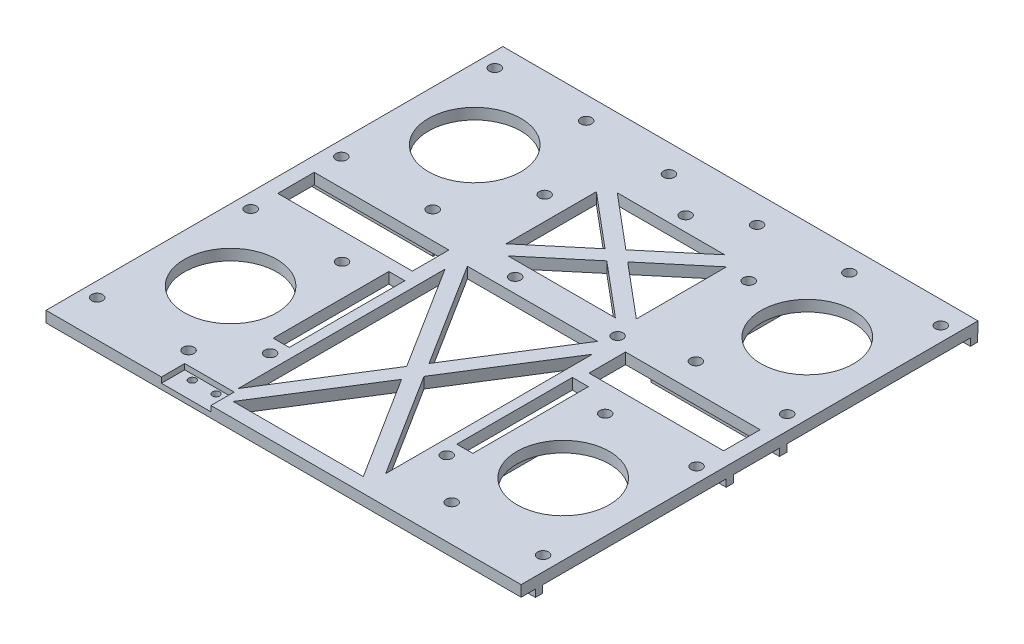
SolidWorks part; units mm, degrees
ref_plane "Front Plane" through (0, 0, 0) normal (0, 0, 1) x (1, 0, 0)
ref_plane "Top Plane" through (0, 0, 0) normal (0, 1, 0) x (1, 0, 0)
ref_plane "Right Plane" through (0, 0, 0) normal (1, 0, 0) x (0, 0, -1)
sketch "Sketch1" plane through (0, 0, 0) normal (0, 1, 0) x (1, 0, 0)
  line L1 (-65, 62.5) -> (65, 62.5)
  line L2 (-65, 62.5) -> (-65, -62.5)
  line L3 (-65, -62.5) -> (65, -62.5)
  line L4 (65, 62.5) -> (65, -62.5)
  line L5 (-65, 62.5) -> (65, -62.5) construction
  line L6 (-65, -62.5) -> (65, 62.5) construction
  point P0 (0, 0)
  dimension "D1" = 130
  dimension "D2" = 125
extrude "Boss-Extrude1" add sketch "Sketch1" along normal blind 5
sketch "Sketch2" plane through (0, 5, 0) normal (0, 1, 0) x (1, 0, 0)
  line L1 (-65, -62.5) -> (65, -62.5) construction
  line L2 (-65, 62.5) -> (-65, -62.5) construction
  circle A0 centre (-61, -52.5) radius 1.5
  circle A1 centre (-36, -52.5) radius 1.5
  circle A2 centre (-36, -10.5) radius 1.5
  circle A3 centre (-61, -10.5) radius 1.5
  circle A4 centre (-45.5, -31.5) radius 12.65
  dimension "D2" = 25.3
  dimension "D7" = 3
  dimension "D8" = 3
  dimension "D9" = 3
  dimension "D10" = 3
  dimension "D1" = 19.5
  dimension "D3" = 31
  dimension "D4" = 4
  dimension "D5" = 10
  dimension "D6" = 10
  dimension "D11" = 4
  dimension "D12" = 42
  dimension "D13" = 42
  dimension "D14" = 25
  dimension "D15" = 25
extrude "Cut-Extrude1" cut sketch "Sketch2" against normal blind 10
ref_plane "Plane1" through (0, 0, 0) normal (-1, 0, 0) x (0, 0, 1)
ref_plane "Plane2" through (0, 0, 0) normal (0, 0, 1) x (1, 0, 0)
mirror "Mirror3" about plane through (0, 0, 0) normal (-1, 0, 0) of "Cut-Extrude1"
sketch "Sketch4" plane through (0, 5, 0) normal (0, 1, 0) x (1, 0, 0)
  line L0 (0, 62.5) -> (0, 47.5) construction
  line L1 (65, 62.5) -> (-65, 62.5) construction
  line L2 (-12.0498, 55) -> (12.0498, 55) construction
  circle A0 centre (0, 47.5) radius 1.5
  circle A1 centre (12.0498, 55) radius 1.5
  circle A2 centre (-12.0498, 55) radius 1.5
  point P9 (0, 55)
  dimension "D2" = 3
  dimension "D3" = 3
  dimension "D4" = 3
  dimension "D1" = 15
  dimension "D5" = 24.0996
extrude "Cut-Extrude3" cut sketch "Sketch4" against normal blind 10
sketch "Sketch5" plane through (0, 0, 0) normal (0, -1, 0) x (1, 0, 0)
  line L0 (-58.15, 31.5) -> (-65, 31.5) construction
  line L1 (-65, -62.5) -> (-65, 62.5) construction
  line L2 (-65, 56.6) -> (-65, 6.4)
  line L3 (-65, 56.6) -> (-31.8, 56.6)
  line L4 (-31.8, 56.6) -> (-31.8, 6.4)
  line L5 (-31.8, 6.4) -> (-65, 6.4)
  line L6 (-65, 58.6) -> (-29.8, 58.6)
  line L7 (-29.8, 58.6) -> (-29.8, 4.4)
  line L8 (-29.8, 4.4) -> (-65, 4.4)
  line L9 (-65, 4.4) -> (-65, 6.4)
  line L10 (-65, 58.6) -> (-65, 56.6)
  circle A0 centre (-45.5, 31.5) radius 12.65 construction
  point P10 (-65, 31.5)
  line M39 (-65, 62.5) -> (-65, -62.5)
  dimension "D1" = 50.2
  dimension "D2" = 33.2
  dimension "D3" = 2
  dimension "D4" = 2
  dimension "D5" = 2
extrude "Boss-Extrude2" add sketch "Sketch5" along normal blind 2 contours L8 L7 L6 L3 L4 L5 M39 region at (-64.3537, 0, 57.6)
mirror "Mirror5" about plane through (0, 0, 0) normal (-1, 0, 0) of "Boss-Extrude2"
ref_plane "Plane3" through (0, 0, 0) normal (0, 0, 1) x (1, 0, 0)
ref_plane "Plane4" through (0, 0, -1.9) normal (0, 0, 1) x (1, 0, 0)
mirror "Mirror7" about plane through (0, 0, -1.9) normal (0, 0, 1) of "Mirror5", "Boss-Extrude2", "Mirror3"
ref_plane "Plane5" through (0, 0, 0) normal (0, -1, 0) x (-1, 0, 0)
sketch "Sketch10" plane through (0, 0, 0) normal (0, -1, 0) x (-1, 0, 0)
  circle A0 centre (-24.17, -42.03) radius 1.5
  circle A1 centre (24.1662, -42.03) radius 1.5
  circle A2 centre (-19.2915, 9.5955) radius 1.5
  circle A3 centre (8.7247, 9.5955) radius 1.5
  circle A4 centre (-24.17, 40.5962) radius 1.5
  circle A5 centre (24.1662, 33.1032) radius 1.5
  circle A6 centre (-19.2915, 9.5955) radius 1.5621 construction
  circle A7 centre (8.7247, 9.5955) radius 1.3153 construction
  circle A8 centre (24.1662, 33.1032) radius 1.5621 construction
  circle A9 centre (-24.17, 40.5962) radius 1.5621 construction
  circle A10 centre (24.1662, -42.03) radius 1.5621 construction
  dimension "D1" = 3
  dimension "D6" = 3
  dimension "D7" = 3
  dimension "D10" = 3
  dimension "D11" = 3
  dimension "D12" = 3
extrude "Cut-Extrude8" cut sketch "Sketch10" against normal through all
sketch "Sketch11" plane through (0, 0, 0) normal (0, -1, 0) x (1, 0, 0)
  circle A0 centre (-12.0498, -55) radius 2.65
  circle A1 centre (0, -47.5) radius 2.65
  circle A2 centre (12.0498, -55) radius 2.65
  circle A3 centre (-24.1662, -33.1032) radius 2.65
  circle A4 centre (24.17, -40.5962) radius 2.65
  circle A5 centre (19.2915, -9.5955) radius 2.65
  circle A6 centre (-8.7247, -9.5955) radius 2.65
  circle A7 centre (-24.1662, 42.03) radius 2.65
  circle A8 centre (24.17, 42.03) radius 2.65
  circle A9 centre (-61, -14.3) radius 2.65
  circle A10 centre (-36, -14.3) radius 2.65
  circle A11 centre (-61, -56.3) radius 2.65
  circle A12 centre (-36, -56.3) radius 2.65
  circle A13 centre (36, -56.3) radius 2.65
  circle A14 centre (61, -56.3) radius 2.65
  circle A15 centre (36, -14.3) radius 2.65
  circle A16 centre (61, -14.3) radius 2.65
  circle A17 centre (36, 10.5) radius 2.65
  circle A18 centre (61, 10.5) radius 2.65
  circle A19 centre (61, 52.5) radius 2.65
  circle A20 centre (36, 52.5) radius 2.65
  circle A21 centre (-36, 52.5) radius 2.65
  circle A22 centre (-36, 10.5) radius 2.65
  circle A23 centre (-61, 10.5) radius 2.65
  circle A24 centre (-61, 52.5) radius 2.65
  dimension "D1" = 5.3
  dimension "D2" = 5.3
  dimension "D3" = 5.3
  dimension "D4" = 5.3
  dimension "D5" = 5.3
  dimension "D6" = 5.3
  dimension "D7" = 5.3
  dimension "D8" = 5.3
  dimension "D9" = 5.3
  dimension "D10" = 5.3
  dimension "D11" = 5.3
  dimension "D12" = 5.3
  dimension "D13" = 5.3
  dimension "D14" = 5.3
  dimension "D15" = 5.3
  dimension "D16" = 5.3
  dimension "D17" = 5.3
  dimension "D18" = 5.3
  dimension "D19" = 5.3
  dimension "D20" = 5.3
  dimension "D21" = 5.3
  dimension "D22" = 5.3
  dimension "D23" = 5.3
  dimension "D24" = 5.3
  dimension "D25" = 5.3
extrude "Cut-Extrude9" cut sketch "Sketch11" against normal blind 0.5
sketch "Sketch12" plane through (0, 5, 0) normal (0, 1, 0) x (1, 0, 0)
  line L0 (-65, -62.5) -> (65, -62.5) construction
  line L1 (-20.1662, 5.5955) -> (20.17, 5.5955)
  line L2 (-20.1662, 5.5955) -> (-20.1662, -58.5)
  line L3 (-20.1662, -58.5) -> (20.17, -58.5)
  line L4 (20.17, 5.5955) -> (20.17, -58.5)
  line L5 (-20.1662, 5.5955) -> (20.17, -58.5) construction
  line L6 (-20.1662, -58.5) -> (20.17, 5.5955) construction
  line L7 (-17.8031, 5.5955) -> (0.0019, -22.6972)
  line L8 (20.17, -54.745) -> (2.365, -26.4522)
  line L9 (2.365, -26.4522) -> (20.17, 1.8405)
  line L10 (0.0019, -22.6972) -> (17.8069, 5.5955)
  line L11 (-20.1662, 1.8405) -> (-2.3612, -26.4522)
  line L12 (-2.3612, -26.4522) -> (-20.1662, -54.745)
  line L13 (-17.8031, -58.5) -> (0.0019, -30.2073)
  line L14 (0.0019, -30.2073) -> (17.8069, -58.5)
  circle A0 centre (-8.7247, 9.5955) radius 1.5 construction
  circle A1 centre (-24.1662, -42.03) radius 1.5 construction
  circle A2 centre (24.17, -42.03) radius 1.5 construction
  dimension "D2" = 4
  dimension "D3" = 4
  dimension "D1" = 4
  dimension "D4" = 4
  dimension "D5" = 2
  dimension "D6" = 2
  dimension "D7" = 2
  dimension "D8" = 2
extrude "Cut-Extrude10" cut sketch "Sketch12" against normal through all contours L12 L11 L2 | L7 L10 L1 | L9 L8 L4 | L14 L13 L3 region at (0.0019, 5, 3.8354) region at (-14.2312, 5, 26.4522) region at (14.235, 5, 26.4522) region at (0.0019, 5, 49.0691)
sketch "Sketch13" plane through (0, 5, 0) normal (0, 1, 0) x (1, 0, 0)
  line L0 (-61, 14.3) -> (-61, -10.5) construction
  line L1 (-61, 1.9) -> (-61, -3.1)
  line L2 (-61, -3.1) -> (-24.1662, -3.1)
  line L3 (-24.1662, -3.1) -> (-24.1662, 6.9)
  line L4 (-24.1662, 6.9) -> (-61, 6.9)
  line L5 (-61, 6.9) -> (-61, 1.9)
  line L6 (-20.1662, 1.8405) -> (-20.1662, -54.745) construction
  dimension "D1" = 10
  dimension "D2" = 5
  dimension "D3" = 4
extrude "Cut-Extrude11" cut sketch "Sketch13" against normal through all
mirror "Mirror9" about plane through (0, 0, 0) normal (-1, 0, 0) of "Cut-Extrude11"
sketch "Sketch14" plane through (0, 5, 0) normal (0, 1, 0) x (1, 0, 0)
  line L0 (-17.8031, 43.5) -> (17.8069, 13.5955) construction
  line L1 (-17.8031, 43.5) -> (17.8069, 43.5)
  line L2 (-17.8031, 43.5) -> (-17.8031, 13.5955)
  line L3 (-17.8031, 13.5955) -> (17.8069, 13.5955)
  line L4 (17.8069, 43.5) -> (17.8069, 13.5955)
  line L5 (-17.8031, 13.5955) -> (17.8069, 43.5) construction
  line L6 (-17.8031, 40.8883) -> (-3.1081, 28.5478)
  line L7 (-3.1081, 28.5478) -> (-17.8031, 16.2072)
  line L8 (-14.6931, 13.5955) -> (0.0019, 25.9361)
  line L9 (0.0019, 25.9361) -> (14.6969, 13.5955)
  line L10 (17.8069, 16.2072) -> (3.1119, 28.5478)
  line L11 (3.1119, 28.5478) -> (17.8069, 40.8883)
  line L12 (14.6969, 43.5) -> (0.0019, 31.1594)
  line L13 (0.0019, 31.1594) -> (-14.6931, 43.5)
  circle A0 centre (0, 47.5) radius 1.5 construction
  circle A1 centre (19.2915, 9.5955) radius 1.5 construction
  dimension "D1" = 4
  dimension "D2" = 4
  dimension "D3" = 2
  dimension "D4" = 2
  dimension "D5" = 2
  dimension "D6" = 2
  dimension "D7" = 2
  dimension "D8" = 2
  dimension "D9" = 2
  dimension "D10" = 2
extrude "Cut-Extrude12" cut sketch "Sketch14" against normal through all contours L7 L6 L2 | L13 L12 L1 | L11 L10 L4 | L9 L8 L3 region at (0.0019, 5, -39.3865) region at (-12.9048, 5, -28.5478) region at (12.9086, 5, -28.5478) region at (0.0019, 5, -17.709)
sketch "Sketch15" plane through (0, 5, 0) normal (0, 1, 0) x (1, 0, 0)
  line L1 (-63.5, 58.8) -> (-58.5, 58.8)
  line L2 (-63.5, 58.8) -> (-63.5, 53.8)
  line L3 (-63.5, 53.8) -> (-58.5, 53.8)
  line L4 (65, -62.5) -> (65, 62.5)
  line L5 (65, 62.5) -> (-65, 62.5)
  line L6 (-65, 62.5) -> (-65, -62.5)
  line L7 (-65, -62.5) -> (65, -62.5)
  line L8 (65, -62.5) -> (65, 62.5)
  line L9 (65, 62.5) -> (-65, 62.5)
  line L10 (-65, 62.5) -> (-65, -62.5)
  line L11 (-65, -62.5) -> (65, -62.5)
  line L12 (-58.5, 58.8) -> (-58.5, 53.8)
  line L13 (-63.5, 58.8) -> (-58.5, 53.8) construction
  line L14 (-63.5, 53.8) -> (-58.5, 58.8) construction
  line L15 (-38.5, 58.8) -> (-33.5, 58.8)
  line L16 (-38.5, 58.8) -> (-38.5, 53.8)
  line L17 (-38.5, 53.8) -> (-33.5, 53.8)
  line L18 (-33.5, 58.8) -> (-33.5, 53.8)
  line L19 (-38.5, 58.8) -> (-33.5, 53.8) construction
  line L20 (-38.5, 53.8) -> (-33.5, 58.8) construction
  line L21 (-14.5498, 57.5) -> (-9.5498, 57.5)
  line L22 (-14.5498, 57.5) -> (-14.5498, 52.5)
  line L23 (-14.5498, 52.5) -> (-9.5498, 52.5)
  line L24 (-9.5498, 57.5) -> (-9.5498, 52.5)
  line L25 (-14.5498, 57.5) -> (-9.5498, 52.5) construction
  line L26 (-14.5498, 52.5) -> (-9.5498, 57.5) construction
  line L27 (-2.5, 50) -> (2.5, 50)
  line L28 (-2.5, 50) -> (-2.5, 45)
  line L29 (-2.5, 45) -> (2.5, 45)
  line L30 (2.5, 50) -> (2.5, 45)
  line L31 (-2.5, 50) -> (2.5, 45) construction
  line L32 (-2.5, 45) -> (2.5, 50) construction
  line L33 (9.5498, 57.5) -> (14.5498, 57.5)
  line L34 (9.5498, 57.5) -> (9.5498, 52.5)
  line L35 (9.5498, 52.5) -> (14.5498, 52.5)
  line L36 (14.5498, 57.5) -> (14.5498, 52.5)
  line L37 (9.5498, 57.5) -> (14.5498, 52.5) construction
  line L38 (9.5498, 52.5) -> (14.5498, 57.5) construction
  line L39 (33.5, 58.8) -> (38.5, 58.8)
  line L40 (33.5, 58.8) -> (33.5, 53.8)
  line L41 (33.5, 53.8) -> (38.5, 53.8)
  line L42 (38.5, 58.8) -> (38.5, 53.8)
  line L43 (33.5, 58.8) -> (38.5, 53.8) construction
  line L44 (33.5, 53.8) -> (38.5, 58.8) construction
  line L45 (63.5, 58.8) -> (58.5, 58.8)
  line L46 (63.5, 58.8) -> (63.5, 53.8)
  line L47 (63.5, 53.8) -> (58.5, 53.8)
  line L48 (58.5, 58.8) -> (58.5, 53.8)
  line L49 (63.5, 58.8) -> (58.5, 53.8) construction
  line L50 (63.5, 53.8) -> (58.5, 58.8) construction
  line L51 (33.5, 16.8) -> (38.5, 16.8)
  line L52 (33.5, 16.8) -> (33.5, 11.8)
  line L53 (33.5, 11.8) -> (38.5, 11.8)
  line L54 (38.5, 16.8) -> (38.5, 11.8)
  line L55 (33.5, 16.8) -> (38.5, 11.8) construction
  line L56 (33.5, 11.8) -> (38.5, 16.8) construction
  line L57 (63.5, 16.8) -> (58.5, 16.8)
  line L58 (63.5, 16.8) -> (63.5, 11.8)
  line L59 (63.5, 11.8) -> (58.5, 11.8)
  line L60 (58.5, 16.8) -> (58.5, 11.8)
  line L61 (63.5, 16.8) -> (58.5, 11.8) construction
  line L62 (63.5, 11.8) -> (58.5, 16.8) construction
  line L63 (21.67, 43.0962) -> (26.67, 43.0962)
  line L64 (21.67, 43.0962) -> (21.67, 38.0962)
  line L65 (21.67, 38.0962) -> (26.67, 38.0962)
  line L66 (26.67, 43.0962) -> (26.67, 38.0962)
  line L67 (21.67, 43.0962) -> (26.67, 38.0962) construction
  line L68 (21.67, 38.0962) -> (26.67, 43.0962) construction
  line L69 (33.5, -8) -> (38.5, -8)
  line L70 (33.5, -8) -> (33.5, -13)
  line L71 (33.5, -13) -> (38.5, -13)
  line L72 (38.5, -8) -> (38.5, -13)
  line L73 (33.5, -8) -> (38.5, -13) construction
  line L74 (33.5, -13) -> (38.5, -8) construction
  line L75 (63.5, -8) -> (58.5, -8)
  line L76 (63.5, -8) -> (63.5, -13)
  line L77 (63.5, -13) -> (58.5, -13)
  line L78 (58.5, -8) -> (58.5, -13)
  line L79 (63.5, -8) -> (58.5, -13) construction
  line L80 (63.5, -13) -> (58.5, -8) construction
  line L81 (21.67, -39.53) -> (26.67, -39.53)
  line L82 (21.67, -39.53) -> (21.67, -44.53)
  line L83 (21.67, -44.53) -> (26.67, -44.53)
  line L84 (26.67, -39.53) -> (26.67, -44.53)
  line L85 (21.67, -39.53) -> (26.67, -44.53) construction
  line L86 (21.67, -44.53) -> (26.67, -39.53) construction
  line L87 (38.5, -50) -> (33.5, -50)
  line L88 (38.5, -50) -> (38.5, -55)
  line L89 (38.5, -55) -> (33.5, -55)
  line L90 (33.5, -50) -> (33.5, -55)
  line L91 (38.5, -50) -> (33.5, -55) construction
  line L92 (38.5, -55) -> (33.5, -50) construction
  line L93 (63.5, -50) -> (58.5, -50)
  line L94 (63.5, -50) -> (63.5, -55)
  line L95 (63.5, -55) -> (58.5, -55)
  line L96 (58.5, -50) -> (58.5, -55)
  line L97 (63.5, -50) -> (58.5, -55) construction
  line L98 (63.5, -55) -> (58.5, -50) construction
  line L99 (-26.6662, -39.53) -> (-21.6662, -39.53)
  line L100 (-26.6662, -39.53) -> (-26.6662, -44.53)
  line L101 (-26.6662, -44.53) -> (-21.6662, -44.53)
  line L102 (-21.6662, -39.53) -> (-21.6662, -44.53)
  line L103 (-26.6662, -39.53) -> (-21.6662, -44.53) construction
  line L104 (-26.6662, -44.53) -> (-21.6662, -39.53) construction
  line L105 (-38.5, -50) -> (-33.5, -50)
  line L106 (-38.5, -50) -> (-38.5, -55)
  line L107 (-38.5, -55) -> (-33.5, -55)
  line L108 (-33.5, -50) -> (-33.5, -55)
  line L109 (-38.5, -50) -> (-33.5, -55) construction
  line L110 (-38.5, -55) -> (-33.5, -50) construction
  line L111 (-38.5, -8) -> (-33.5, -8)
  line L112 (-38.5, -8) -> (-38.5, -13)
  line L113 (-38.5, -13) -> (-33.5, -13)
  line L114 (-33.5, -8) -> (-33.5, -13)
  line L115 (-38.5, -8) -> (-33.5, -13) construction
  line L116 (-38.5, -13) -> (-33.5, -8) construction
  line L117 (16.7915, 12.0955) -> (21.7915, 12.0955)
  line L118 (16.7915, 12.0955) -> (16.7915, 7.0955)
  line L119 (16.7915, 7.0955) -> (21.7915, 7.0955)
  line L120 (21.7915, 12.0955) -> (21.7915, 7.0955)
  line L121 (16.7915, 12.0955) -> (21.7915, 7.0955) construction
  line L122 (16.7915, 7.0955) -> (21.7915, 12.0955) construction
  line L123 (-11.2247, 12.0955) -> (-6.2247, 12.0955)
  line L124 (-11.2247, 12.0955) -> (-11.2247, 7.0955)
  line L125 (-11.2247, 7.0955) -> (-6.2247, 7.0955)
  line L126 (-6.2247, 12.0955) -> (-6.2247, 7.0955)
  line L127 (-11.2247, 12.0955) -> (-6.2247, 7.0955) construction
  line L128 (-11.2247, 7.0955) -> (-6.2247, 12.0955) construction
  line L129 (-26.6662, 35.6032) -> (-21.6662, 35.6032)
  line L130 (-26.6662, 35.6032) -> (-26.6662, 30.6032)
  line L131 (-26.6662, 30.6032) -> (-21.6662, 30.6032)
  line L132 (-21.6662, 35.6032) -> (-21.6662, 30.6032)
  line L133 (-26.6662, 35.6032) -> (-21.6662, 30.6032) construction
  line L134 (-26.6662, 30.6032) -> (-21.6662, 35.6032) construction
  line L135 (-63.5, 16.8) -> (-58.5, 16.8)
  line L136 (-63.5, 16.8) -> (-63.5, 11.8)
  line L137 (-63.5, 11.8) -> (-58.5, 11.8)
  line L138 (-58.5, 16.8) -> (-58.5, 11.8)
  line L139 (-63.5, 16.8) -> (-58.5, 11.8) construction
  line L140 (-63.5, 11.8) -> (-58.5, 16.8) construction
  line L141 (-38.5, 16.8) -> (-33.5, 16.8)
  line L142 (-38.5, 16.8) -> (-38.5, 11.8)
  line L143 (-38.5, 11.8) -> (-33.5, 11.8)
  line L144 (-33.5, 16.8) -> (-33.5, 11.8)
  line L145 (-38.5, 16.8) -> (-33.5, 11.8) construction
  line L146 (-38.5, 11.8) -> (-33.5, 16.8) construction
  line L147 (-63.5, -8) -> (-58.5, -8)
  line L148 (-63.5, -8) -> (-63.5, -13)
  line L149 (-63.5, -13) -> (-58.5, -13)
  line L150 (-58.5, -8) -> (-58.5, -13)
  line L151 (-63.5, -8) -> (-58.5, -13) construction
  line L152 (-63.5, -13) -> (-58.5, -8) construction
  line L153 (-63.5, -50) -> (-58.5, -50)
  line L154 (-63.5, -50) -> (-63.5, -55)
  line L155 (-63.5, -55) -> (-58.5, -55)
  line L156 (-58.5, -50) -> (-58.5, -55)
  line L157 (-63.5, -50) -> (-58.5, -55) construction
  line L158 (-63.5, -55) -> (-58.5, -50) construction
  circle A0 centre (-61, 56.3) radius 1.5 construction
  circle A1 centre (-36, 56.3) radius 1.5 construction
  circle A2 centre (-12.0498, 55) radius 1.5 construction
  circle A3 centre (0, 47.5) radius 1.5 construction
  circle A4 centre (12.0498, 55) radius 1.5 construction
  circle A5 centre (36, 56.3) radius 1.5 construction
  circle A6 centre (61, 56.3) radius 1.5 construction
  circle A7 centre (24.17, 40.5962) radius 1.5 construction
  circle A8 centre (36, 14.3) radius 1.5 construction
  circle A9 centre (61, 14.3) radius 1.5 construction
  circle A10 centre (-24.1662, 33.1032) radius 1.5 construction
  circle A11 centre (-61, 14.3) radius 1.5 construction
  circle A12 centre (-36, 14.3) radius 1.5 construction
  circle A13 centre (-8.7247, 9.5955) radius 1.5 construction
  circle A14 centre (19.2915, 9.5955) radius 1.5 construction
  circle A15 centre (-61, -10.5) radius 1.5 construction
  circle A16 centre (-36, -10.5) radius 1.5 construction
  circle A17 centre (36, -10.5) radius 1.5 construction
  circle A18 centre (61, -10.5) radius 1.5 construction
  circle A19 centre (61, -52.5) radius 1.5 construction
  circle A20 centre (36, -52.5) radius 1.5 construction
  circle A21 centre (24.17, -42.03) radius 1.5 construction
  circle A22 centre (-24.1662, -42.03) radius 1.5 construction
  circle A23 centre (-36, -52.5) radius 1.5 construction
  circle A24 centre (-61, -52.5) radius 1.5 construction
  point P2 (-61, 56.3)
  point P12 (-36, 56.3)
  point P20 (-12.0498, 55)
  point P26 (0, 47.5)
  point P32 (12.0498, 55)
  point P38 (36, 56.3)
  point P44 (61, 56.3)
  point P50 (36, 14.3)
  point P56 (61, 14.3)
  point P62 (24.17, 40.5962)
  point P84 (36, -10.5)
  point P90 (61, -10.5)
  point P96 (24.17, -42.03)
  point P102 (36, -52.5)
  point P108 (61, -52.5)
  point P114 (-24.1662, -42.03)
  point P120 (-36, -52.5)
  point P126 (-36, -10.5)
  point P132 (19.2915, 9.5955)
  point P138 (-8.7247, 9.5955)
  point P144 (-24.1662, 33.1032)
  point P150 (-61, 14.3)
  point P156 (-36, 14.3)
  point P162 (-61, -10.5)
  point P168 (-61, -52.5)
  dimension "D2" = 2.5
  dimension "D3" = 2.5
  dimension "D4" = 2.5
  dimension "D5" = 2.5
  dimension "D6" = 2.5
  dimension "D7" = 2.5
  dimension "D8" = 2.5
  dimension "D9" = 2.5
  dimension "D10" = 2.5
  dimension "D11" = 2.5
  dimension "D12" = 2.5
  dimension "D13" = 2.5
  dimension "D15" = 2.5
  dimension "D16" = 2.5
  dimension "D17" = 2.5
  dimension "D18" = 2.5
  dimension "D19" = 2.5
  dimension "D20" = 2.5
  dimension "D21" = 2.5
  dimension "D22" = 2.5
  dimension "D23" = 2.5
  dimension "D24" = 2.5
  dimension "D25" = 2.5
  dimension "D26" = 2.5
  dimension "D27" = 2.5
  dimension "D28" = 2.5
  dimension "D29" = 2.5
  dimension "D30" = 2.5
  dimension "D31" = 2.5
  dimension "D32" = 2.5
  dimension "D33" = 2.5
  dimension "D34" = 2.5
  dimension "D35" = 2.5
  dimension "D36" = 2.5
  dimension "D37" = 2.5
  dimension "D38" = 2.5
  dimension "D39" = 2.5
  dimension "D40" = 2.5
  dimension "D41" = 2.5
  dimension "D42" = 2.5
  dimension "D43" = 2.5
  dimension "D44" = 2.5
  dimension "D45" = 2.5
  dimension "D46" = 2.5
  dimension "D47" = 2.5
  dimension "D48" = 2.5
  dimension "D49" = 2.5
  dimension "D14" = 2.5
  dimension "D1" = 0
extrude "Cut-Extrude14" cut sketch "Sketch15" against normal blind 2
ref_plane "Plane6" through (0, 13, 0) normal (0, 1, 0) x (1, 0, 0)
sketch "Sketch17" plane through (0, 13, 0) normal (0, 1, 0) x (1, 0, 0)
  line L1 (-68.0587, 64.2777) -> (69.5711, 64.2777)
  line L2 (-68.0587, 64.2777) -> (-68.0587, -66.7984)
  line L3 (-68.0587, -66.7984) -> (69.5711, -66.7984)
  line L4 (69.5711, 64.2777) -> (69.5711, -66.7984)
extrude "Cut-Extrude15" cut sketch "Sketch17" against normal blind 2 from surface starting at face at (-61, 5, -15.8)
sketch "Sketch18" plane through (0, 3, 0) normal (0, 1, 0) x (1, 0, 0)
  line L0 (-65, -62.5) -> (65, -62.5) construction
  line L1 (-33.412, -56.1297) -> (-19.8846, -56.1297)
  line L2 (-33.412, -56.1297) -> (-33.412, -62.5)
  line L3 (-33.412, -62.5) -> (-19.8846, -62.5)
  line L4 (-19.8846, -56.1297) -> (-19.8846, -62.5)
extrude "Cut-Extrude16" cut sketch "Sketch18" against normal blind 1.5
sketch "Sketch19" plane through (0, 1.5, 0) normal (0, 1, 0) x (1, 0, 0)
  circle A0 centre (-23.4163, -57.55) radius 1
  circle A1 centre (-29.9163, -57.55) radius 1
extrude "Cut-Extrude17" cut sketch "Sketch19" against normal blind 5
sketch "Sketch20" plane through (0, 0, 0) normal (0, -1, 0) x (1, 0, 0)
  line L1 (-32.8112, 59.7055) -> (-26.1535, 59.7055)
  line L2 (-32.8112, 59.7055) -> (-32.8112, 55.2822)
  line L3 (-32.8112, 55.2822) -> (-26.1535, 55.2822)
  line L4 (-26.1535, 59.7055) -> (-26.1535, 55.2822)
extrude "Cut-Extrude18" cut sketch "Sketch20" along normal up to surface (2 mm away) up to face at (-44.3916, -2, 36.71)
sketch "Sketch21" plane through (0, 0, 0) normal (0, -1, 0) x (-1, 0, 0)
  line L0 (-29.8, -58.6) -> (-29.8, -4.4) construction
  line L1 (-27.3, -6.4) -> (-22.9235, -6.4)
  line L2 (-27.3, -6.4) -> (-27.3, -38.03)
  line L3 (-27.3, -38.03) -> (-22.9235, -38.03)
  line L4 (-22.9235, -6.4) -> (-22.9235, -38.03)
  line L5 (22.9162, -6.4) -> (27.3, -6.4)
  line L6 (22.9162, -6.4) -> (22.9162, -38.03)
  line L7 (22.9162, -38.03) -> (27.3, -38.03)
  line L8 (27.3, -6.4) -> (27.3, -38.03)
  line L11 (29.8, -55.2822) -> (29.8, -4.4) construction
  line L12 (-20.17, 1.8405) -> (-20.17, -54.745) construction
  line L13 (20.1662, 1.8405) -> (20.1662, -54.745) construction
  line L14 (31.8, -6.4) -> (65, -6.4) construction
  circle A0 centre (-24.17, -42.03) radius 2.65 construction
  dimension "D5" = 4
  dimension "D1" = 2.5
  dimension "D2" = 2.5
  dimension "D3" = 2.7535
  dimension "D4" = 2.75
extrude "Cut-Extrude19" cut sketch "Sketch21" against normal blind 7.4
